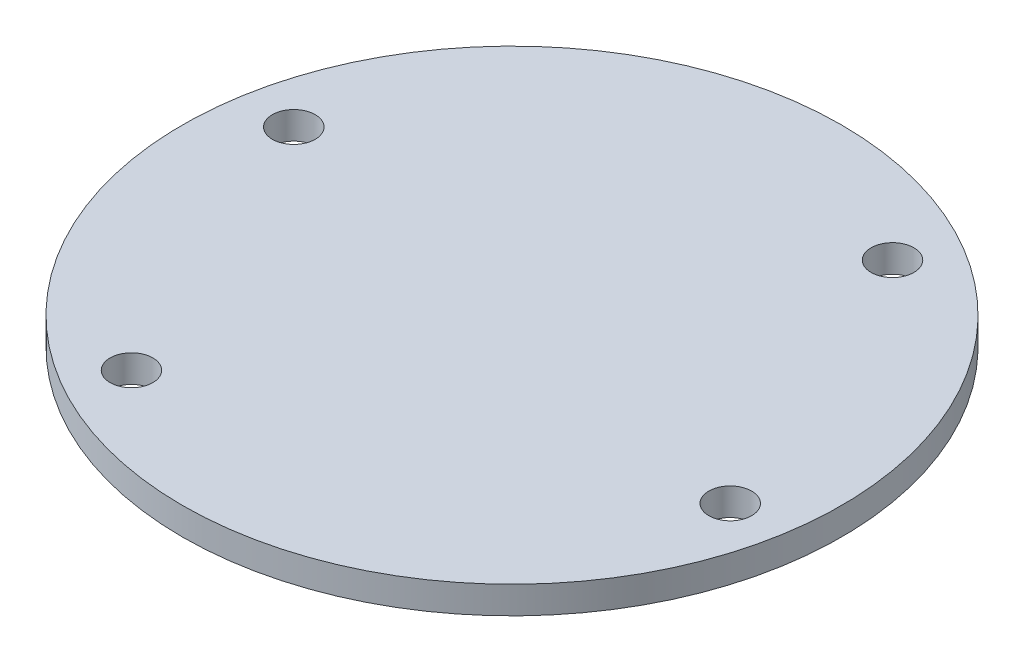
SolidWorks part; units mm, degrees
ref_plane "Front Plane" through (0, 0, 0) normal (0, 0, 1) x (1, 0, 0)
ref_plane "Top Plane" through (0, 0, 0) normal (0, 1, 0) x (1, 0, 0)
ref_plane "Right Plane" through (0, 0, 0) normal (1, 0, 0) x (0, 0, -1)
sketch "Sketch1" plane through (0, 0, 0) normal (0, 1, 0) x (1, 0, 0)
  circle A0 centre (0, 0) radius 19.25
  dimension "D1" = 38.5
extrude "Boss-Extrude1" add sketch "Sketch1" along normal blind 1.6
sketch "Sketch3" plane through (0, 1.6, 0) normal (0, 1, 0) x (1, 0, 0)
  circle A9 centre (-15.8938, 3.1472) radius 1.25
  circle A10 centre (8.3271, 13.8988) radius 1.25
  circle A11 centre (15.8938, -3.1472) radius 1.25
  circle A12 centre (-8.3278, -13.8998) radius 1.25
extrude "Cut-Extrude1" cut sketch "Sketch3" against normal through all contours A9 | A12 | A11 | A10 region at (-15.8938, 1.6, -3.1472) region at (8.3271, 1.6, -13.8988) region at (15.8938, 1.6, 3.1472) region at (-8.3278, 1.6, 13.8998)
